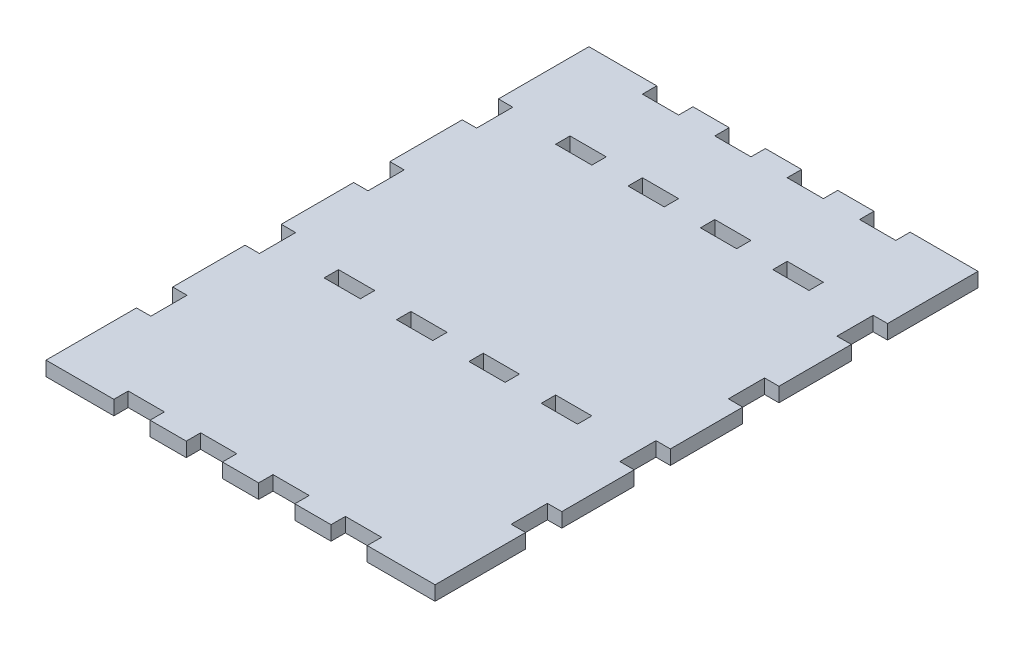
SolidWorks part; units mm, degrees
ref_plane "Front Plane" through (0, 0, 0) normal (0, 0, 1) x (1, 0, 0)
ref_plane "Top Plane" through (0, 0, 0) normal (0, 1, 0) x (1, 0, 0)
ref_plane "Right Plane" through (0, 0, 0) normal (1, 0, 0) x (0, 0, -1)
sketch "Sketch1" plane through (0, 0, 0) normal (0, 1, 0) x (1, 0, 0)
  line L1 (0, 0) -> (86, 0)
  line L2 (0, 0) -> (0, -120)
  line L3 (0, -120) -> (86, -120)
  line L4 (86, 0) -> (86, -120)
  dimension "D1" = 120
  dimension "D2" = 86
extrude "Boss-Extrude1" add sketch "Sketch1" along normal blind 3.175
sketch "Sketch2" plane through (0, 3.175, 0) normal (0, 1, 0) x (1, 0, 0)
  line L0 (43, 0) -> (43, -120) construction
  line L1 (86, 0) -> (0, 0) construction
  line L2 (0, -120) -> (86, -120) construction
  line L3 (63, 0) -> (63, -3.175)
  line L4 (47, 0) -> (55, 0)
  line L5 (47, 0) -> (47, -3.175)
  line L6 (47, -3.175) -> (55, -3.175)
  line L7 (55, 0) -> (55, -3.175)
  line L8 (63, 0) -> (71, 0)
  line L9 (63, -3.175) -> (71, -3.175)
  line L10 (71, 0) -> (71, -3.175)
  line L11 (15, 0) -> (15, -3.175)
  line L12 (23, -3.175) -> (15, -3.175)
  line L13 (23, 0) -> (15, 0)
  line L14 (31, 0) -> (31, -3.175)
  line L15 (39, -3.175) -> (31, -3.175)
  line L16 (39, 0) -> (39, -3.175)
  line L17 (39, 0) -> (31, 0)
  line L18 (23, 0) -> (23, -3.175)
  line L19 (86, -60) -> (0, -60) construction
  line L20 (86, -120) -> (86, 0) construction
  line L21 (0, 0) -> (0, -120) construction
  line L22 (0, -28) -> (3.175, -28)
  line L23 (0, -52) -> (3.175, -52)
  line L24 (0, -52) -> (0, -44)
  line L25 (0, -44) -> (3.175, -44)
  line L26 (3.175, -52) -> (3.175, -44)
  line L27 (0, -28) -> (0, -20)
  line L28 (0, -20) -> (3.175, -20)
  line L29 (3.175, -28) -> (3.175, -20)
  line L30 (3.175, -92) -> (3.175, -100)
  line L31 (0, -100) -> (3.175, -100)
  line L32 (0, -92) -> (0, -100)
  line L33 (3.175, -68) -> (3.175, -76)
  line L34 (0, -76) -> (3.175, -76)
  line L35 (0, -68) -> (0, -76)
  line L36 (0, -68) -> (3.175, -68)
  line L37 (0, -92) -> (3.175, -92)
  line L38 (23, -120) -> (23, -116.825)
  line L39 (39, -120) -> (31, -120)
  line L40 (39, -120) -> (39, -116.825)
  line L41 (39, -116.825) -> (31, -116.825)
  line L42 (31, -120) -> (31, -116.825)
  line L43 (23, -120) -> (15, -120)
  line L44 (23, -116.825) -> (15, -116.825)
  line L45 (15, -120) -> (15, -116.825)
  line L46 (71, -120) -> (71, -116.825)
  line L47 (63, -116.825) -> (71, -116.825)
  line L48 (63, -120) -> (71, -120)
  line L49 (55, -120) -> (55, -116.825)
  line L50 (47, -116.825) -> (55, -116.825)
  line L51 (47, -120) -> (47, -116.825)
  line L52 (47, -120) -> (55, -120)
  line L53 (63, -120) -> (63, -116.825)
  line L54 (86, -92) -> (82.825, -92)
  line L55 (86, -68) -> (82.825, -68)
  line L56 (86, -68) -> (86, -76)
  line L57 (86, -76) -> (82.825, -76)
  line L58 (82.825, -68) -> (82.825, -76)
  line L59 (86, -92) -> (86, -100)
  line L60 (86, -100) -> (82.825, -100)
  line L61 (82.825, -92) -> (82.825, -100)
  line L62 (82.825, -28) -> (82.825, -20)
  line L63 (86, -20) -> (82.825, -20)
  line L64 (86, -28) -> (86, -20)
  line L65 (82.825, -52) -> (82.825, -44)
  line L66 (86, -44) -> (82.825, -44)
  line L67 (86, -52) -> (86, -44)
  line L68 (86, -52) -> (82.825, -52)
  line L69 (86, -28) -> (82.825, -28)
  dimension "D1" = 8
  dimension "D2" = 4
  dimension "D4" = 3.175
  dimension "D5" = 3.175
  dimension "D6" = 8
  dimension "D7" = 8
  dimension "D3" = 2
  dimension "D8" = 2
extrude "Cut-Extrude1" cut sketch "Sketch2" against normal up to next
sketch "Sketch3" plane through (0, 3.175, 0) normal (0, 1, 0) x (1, 0, 0)
  line L0 (0, -19.175) -> (86, -19.175) construction
  line L1 (0, -28) -> (0, -44) construction
  line L2 (86, -44) -> (86, -28) construction
  line L3 (15, -3.175) -> (23, -3.175) construction
  line L4 (43, 0) -> (43, -120) construction
  line L5 (47, 0) -> (39, 0) construction
  line L6 (39, -120) -> (47, -120) construction
  line L7 (63, -19.175) -> (71, -19.175)
  line L8 (47, -19.175) -> (55, -19.175)
  line L9 (47, -19.175) -> (47, -22.35)
  line L10 (47, -22.35) -> (55, -22.35)
  line L11 (55, -19.175) -> (55, -22.35)
  line L12 (63, -19.175) -> (63, -22.35)
  line L13 (63, -22.35) -> (71, -22.35)
  line L14 (71, -19.175) -> (71, -22.35)
  line L15 (15, -19.175) -> (15, -22.35)
  line L16 (23, -22.35) -> (15, -22.35)
  line L17 (23, -19.175) -> (23, -22.35)
  line L18 (31, -19.175) -> (31, -22.35)
  line L19 (39, -22.35) -> (31, -22.35)
  line L20 (39, -19.175) -> (39, -22.35)
  line L21 (39, -19.175) -> (31, -19.175)
  line L22 (23, -19.175) -> (15, -19.175)
  dimension "D1" = 16
  dimension "D2" = 3.175
  dimension "D3" = 8
  dimension "D4" = 4
  dimension "D5" = 2
extrude "Cut-Extrude2" cut sketch "Sketch3" against normal up to next
sketch "Sketch4" plane through (0, 3.175, 0) normal (0, 1, 0) x (1, 0, 0)
  line L0 (0, -73.525) -> (86, -73.525) construction
  line L1 (0, -76) -> (0, -92) construction
  line L2 (86, -92) -> (86, -76) construction
  line L3 (63, -3.175) -> (71, -3.175) construction
  line L4 (43, 0) -> (43, -120) construction
  line L5 (63, -70.35) -> (71, -70.35)
  line L6 (47, -70.35) -> (55, -70.35)
  line L7 (47, -70.35) -> (47, -73.525)
  line L8 (47, -73.525) -> (55, -73.525)
  line L9 (55, -70.35) -> (55, -73.525)
  line L10 (63, -70.35) -> (63, -73.525)
  line L11 (63, -73.525) -> (71, -73.525)
  line L12 (71, -70.35) -> (71, -73.525)
  line L13 (15, -70.35) -> (15, -73.525)
  line L14 (23, -73.525) -> (15, -73.525)
  line L15 (23, -70.35) -> (23, -73.525)
  line L16 (31, -70.35) -> (31, -73.525)
  line L17 (39, -73.525) -> (31, -73.525)
  line L18 (39, -70.35) -> (39, -73.525)
  line L19 (39, -70.35) -> (31, -70.35)
  line L20 (23, -70.35) -> (15, -70.35)
  line L21 (47, 0) -> (39, 0) construction
  point P26 (43, -73.525)
  dimension "D1" = 70.35
  dimension "D2" = 3.175
  dimension "D3" = 8
  dimension "D4" = 4
  dimension "D5" = 0
  dimension "D6" = 8
  dimension "D7" = 0
  dimension "D8" = 0
  dimension "D9" = 8
  dimension "D10" = 0
  dimension "D11" = 0
  dimension "D12" = 3.175
extrude "Cut-Extrude3" cut sketch "Sketch4" against normal up to next
